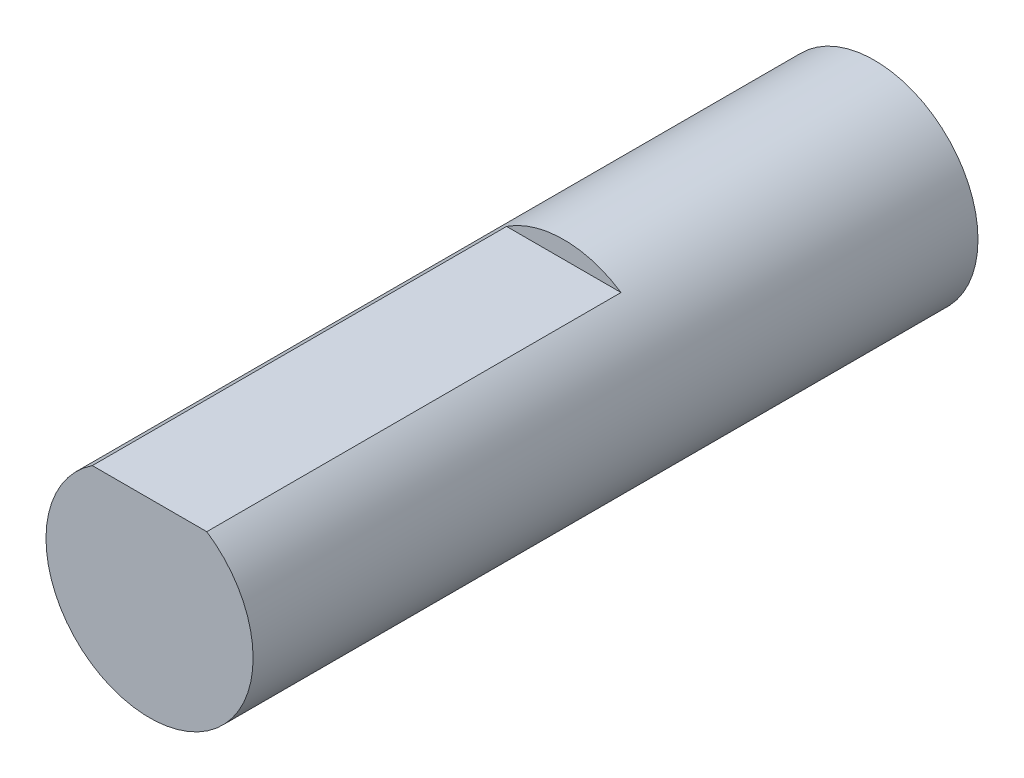
SolidWorks part; units mm, degrees
ref_plane "Front Plane" through (0, 0, 0) normal (0, 0, 1) x (1, 0, 0)
ref_plane "Top Plane" through (0, 0, 0) normal (0, 1, 0) x (1, 0, 0)
ref_plane "Right Plane" through (0, 0, 0) normal (1, 0, 0) x (0, 0, -1)
sketch "Sketch1" plane through (0, 0, 0) normal (0, 0, 1) x (1, 0, 0)
  line L0 (-1.6583, 2.5) -> (1.6583, 2.5)
  circle A0 centre (0, 0) radius 3
  dimension "D1" = 6
  dimension "D2" = 2.5
extrude "Boss-Extrude1" add sketch "Sketch1" along normal blind 21 contours L0 A0 | L0 A0 region at (0, 2.7015, 0) region at (0, -0.112, 0)
extrude "Cut-Extrude1" cut sketch "Sketch1<3>" against normal blind 12 from surface contours L0 A0 region at (0, 2.7015, 0) starting at face at (3, 0, 21)
sketch "Sketch1<3>" plane through (0, 0, 0) normal (0, 0, 1) x (1, 0, 0) same geometry as "Sketch1"
